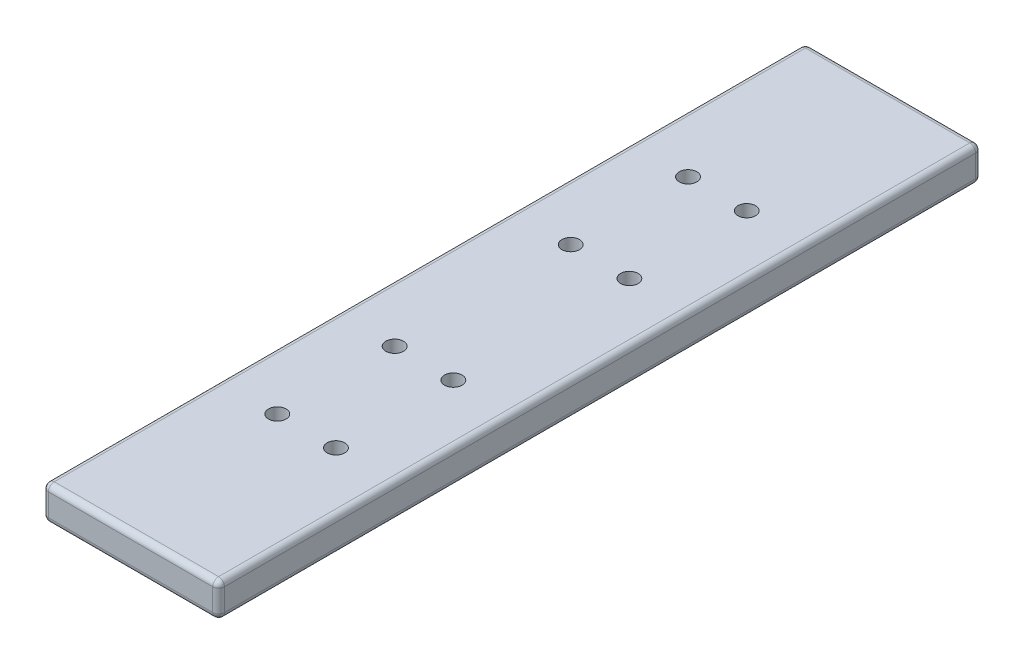
SolidWorks part; units mm, degrees
ref_plane "Front Plane" through (0, 0, 0) normal (0, 0, 1) x (1, 0, 0)
ref_plane "Top Plane" through (0, 0, 0) normal (0, 1, 0) x (1, 0, 0)
ref_plane "Right Plane" through (0, 0, 0) normal (1, 0, 0) x (0, 0, -1)
sketch "Sketch2" plane through (0, 0, 0) normal (0, 0, 1) x (1, 0, 0)
  line L1 (-15, -2.9) -> (15, -2.9)
  line L2 (-15, -2.9) -> (-15, 2.9)
  line L3 (-15, 2.9) -> (15, 2.9)
  line L4 (15, -2.9) -> (15, 2.9)
  line L5 (0, 2.9) -> (0, -2.9) construction
  line L6 (-15, 0) -> (15, 0) construction
  point P0 (0, 0)
  dimension "D1" = 5.8
  dimension "D2" = 30
extrude "Boss-Extrude1" add sketch "Sketch2" along normal blind 130
sketch "Sketch3" plane through (0, 2.9, 0) normal (0, 1, 0) x (1, 0, 0)
  line L0 (-15, -65) -> (15, -65) construction
  line L1 (-15, -130) -> (-15, 0) construction
  line L2 (15, -130) -> (15, 0) construction
  line L3 (-5, -130) -> (-5, -100) construction
  line L4 (15, -130) -> (-15, -130) construction
  line L5 (-5, -100) -> (-15, -100) construction
  circle A0 centre (-5, -100) radius 1.5
  circle A1 centre (5, -100) radius 1.5
  circle A2 centre (5, -80) radius 1.5
  circle A3 centre (-5, -80) radius 1.5
  circle A4 centre (-5, -50) radius 1.5
  circle A5 centre (5, -50) radius 1.5
  circle A6 centre (5, -30) radius 1.5
  circle A7 centre (-5, -30) radius 1.5
  dimension "D3" = 3
  dimension "D4" = 2
  dimension "D5" = 2
  dimension "D1" = 30
  dimension "D2" = 10
extrude "Cut-Extrude3" cut sketch "Sketch3" against normal through all
fillet "Fillet1" radius 1 12 edges at (15, 0, 0) (-15, 0, 0) (-15, 0, 130) (15, 0, 130) (-15, -2.9, 65) (0, -2.9, 130) (15, -2.9, 65) (0, -2.9, 0) (15, 2.9, 65) (0, 2.9, 130) (-15, 2.9, 65) (0, 2.9, 0)
